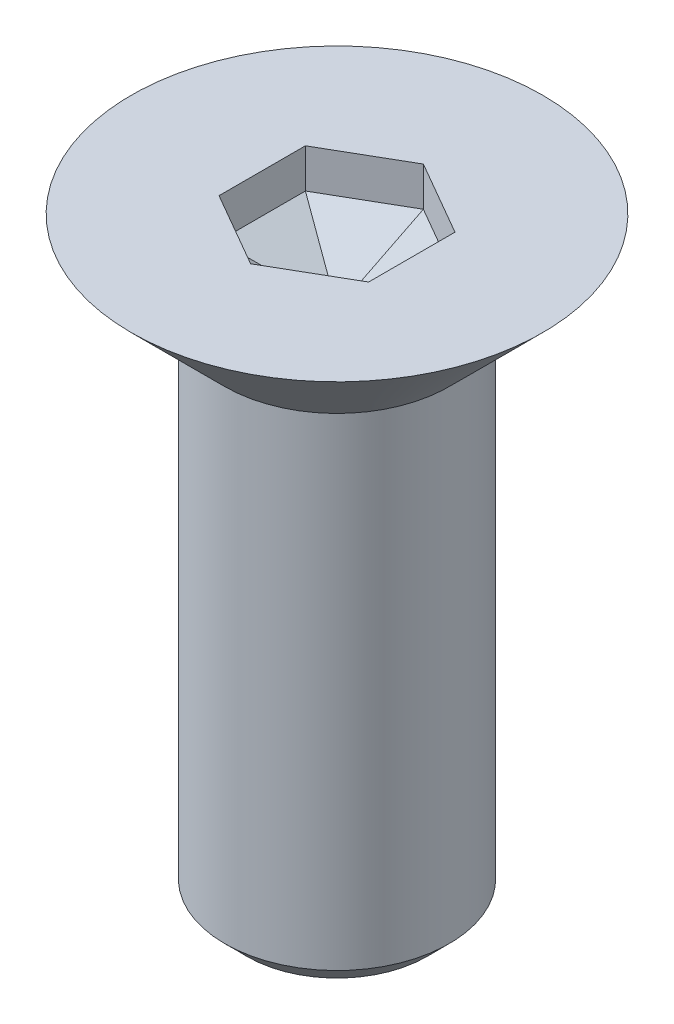
SolidWorks part; units mm, degrees
ref_plane "前视基准面" through (0, 0, 0) normal (0, 0, 1) x (1, 0, 0)
ref_plane "上视基准面" through (0, 0, 0) normal (0, 1, 0) x (1, 0, 0)
ref_plane "右视基准面" through (0, 0, 0) normal (1, 0, 0) x (0, 0, -1)
sketch "草图2" plane through (0, 0, 0) normal (0, 0, 1) x (1, 0, 0)
  line L0 (0, -1.86) -> (0, 0)
  line L1 (0, 0) -> (2.75, 0)
  line L2 (2.75, 0) -> (0.89, -1.86)
  line L3 (0.89, -1.86) -> (0, -1.86)
  dimension "D1" = 45
  dimension "k" = 1.86
  dimension "dk/2" = 2.75
revolve "旋转1" add sketch "草图2" angle 360 about L0
sketch "草图4" plane through (0, 0, 0) normal (0, -1, 0) x (1, 0, 0)
  circle A0 centre (0, 0) radius 1.5
  dimension "d" = 3
extrude "凸台-拉伸2" add sketch "草图4" along normal blind 8
cosmetic thread "装饰螺纹线1" parameters "b"=12, "D2"=2.459
sketch "草图3" plane through (0, 0, 0) normal (0, 1, 0) x (1, 0, 0)
  line L1 (1, 0.5774) -> (0, 1.1547)
  line L2 (0, 1.1547) -> (-1, 0.5774)
  line L3 (-1, 0.5774) -> (-1, -0.5774)
  line L4 (-1, -0.5774) -> (0, -1.1547)
  line L5 (0, -1.1547) -> (1, -0.5774)
  line L6 (1, -0.5774) -> (1, 0.5774)
  circle A0 centre (0, 0) radius 1 construction
  dimension "S" = 2
extrude "切除-拉伸1" cut sketch "草图3" against normal blind 1.1
chamfer "倒角3" distance 0.5764 angle 60 6 edges at (-0.5, -1.1, 0.866) (-1, -1.1, 0) (-0.5, -1.1, -0.866) (0.5, -1.1, -0.866) (1, -1.1, 0) (0.5, -1.1, 0.866) first distance on face at (-0.5, -0.55, 0.866) first distance on face at (-1, -0.55, 0) first distance on face at (-0.5, -0.55, -0.866) first distance on face at (0.5, -0.55, -0.866) first distance on face at (1, -0.55, 0) first distance on face at (0.5, -0.55, 0.866)
chamfer "倒角4" distance 0.3 angle 45 1 edges at (0, -8, -1.5)
ref_axis "基准轴1" through (0, -7.7, 0) along (0, 1, 0)
ref_plane "基准面1" through (0, 0, 0) normal (0, -1, 0) x (-1, 0, 0)
equation "\"D1@倒角3\"= \"S@草图3\" / 3.47"
equation "\"D1@倒角4\"= \"d@草图4\" / 10"
